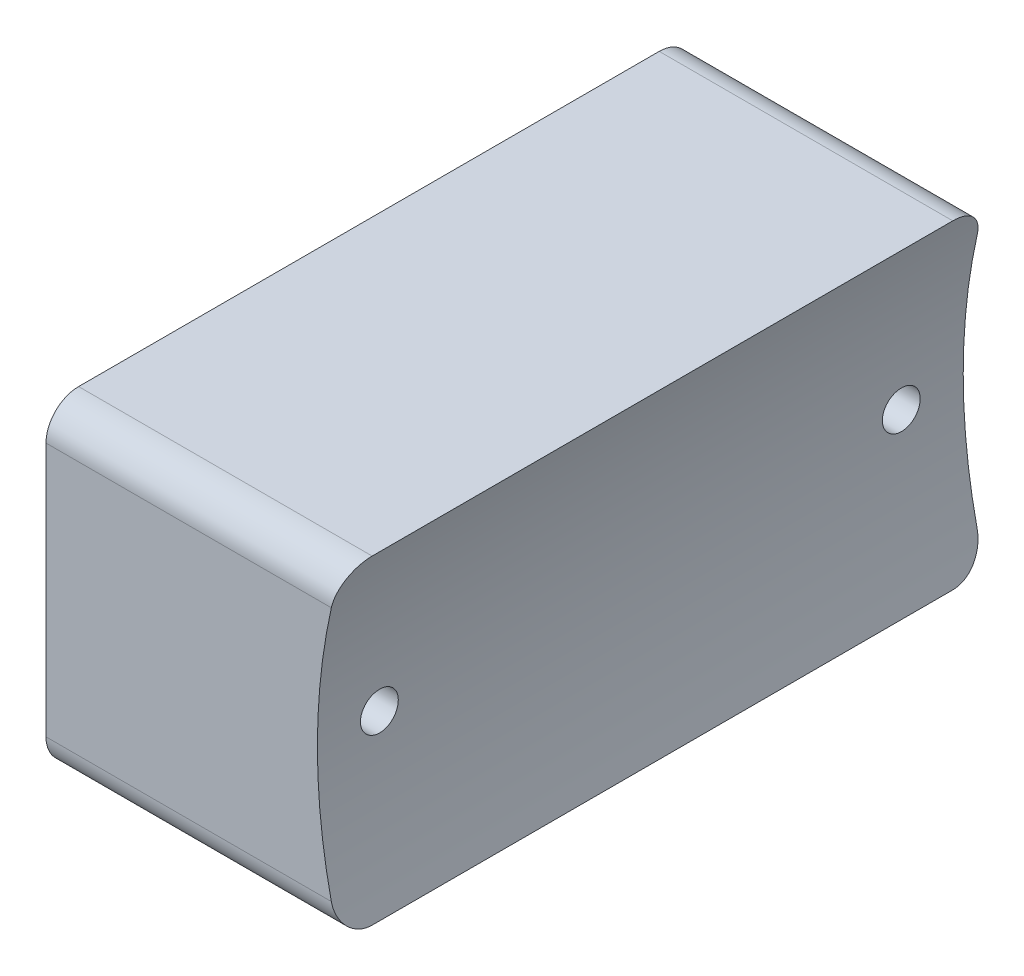
SolidWorks part; units mm, degrees
ref_plane "Спереди" through (0, 0, 0) normal (0, 0, 1) x (1, 0, 0)
ref_plane "Сверху" through (0, 0, 0) normal (0, 1, 0) x (1, 0, 0)
ref_plane "Справа" through (0, 0, 0) normal (1, 0, 0) x (0, 0, -1)
sketch "Эскиз1" plane through (0, 0, 0) normal (1, 0, 0) x (0, 0, -1)
  line L0 (-1050, 0) -> (48950, 0) construction
  line L1 (0, -1021.7777) -> (0, 48978.2223) construction
  line L2 (-24.75, -12.25) -> (24.75, -12.25)
  line L3 (-24.75, -12.25) -> (-24.75, 12.25)
  line L4 (-24.75, 12.25) -> (24.75, 12.25)
  line L5 (24.75, -12.25) -> (24.75, 12.25)
  line L6 (-24.75, -12.25) -> (24.75, 12.25) construction
  line L7 (-24.75, 12.25) -> (24.75, -12.25) construction
  point P3 (0, 0)
  dimension "D1" = 24.5
  dimension "D2" = 49.5
extrude "Бобышка-Вытянуть1" add sketch "Эскиз1" along normal blind 22.5
sketch "Эскиз2" plane through (0, 0, 0) normal (-1, 0, 0) x (0, 0, 1)
  line L1 (-24.75, -12.25) -> (-24.75, 12.25) construction
  line L2 (24.75, 12.25) -> (24.75, -12.25) construction
  line L3 (24.75, -12.25) -> (-24.75, -12.25) construction
  circle A0 centre (-20, -7.25) radius 2.5
  circle A1 centre (20, -7.25) radius 2.5
  dimension "D3" = 5
  dimension "D1" = 5
  dimension "D2" = 4.75
  dimension "D4" = 4.75
  dimension "D5" = 5
extrude "Вырез-Вытянуть1" cut sketch "Эскиз2" against normal blind 3
sketch "Эскиз3" plane through (0, 0, 0) normal (-1, 0, 0) x (0, 0, 1)
  line L0 (0, -1000) -> (0, 49000) construction
  line L2 (-7.6, 7.5) -> (7.6, 7.5)
  line L3 (-7.6, 7.5) -> (-7.6, 10)
  line L4 (-7.6, 10) -> (7.6, 10)
  line L5 (7.6, 7.5) -> (7.6, 10)
  line L6 (-7.6, 7.5) -> (7.6, 10) construction
  line L7 (-7.6, 10) -> (7.6, 7.5) construction
  line L8 (-24.75, 12.25) -> (24.75, 12.25) construction
  point P1 (0, 8.75)
  dimension "D1" = 15.2
  dimension "D2" = 2.5
  dimension "D3" = 2.25
extrude "Вырез-Вытянуть2" cut sketch "Эскиз3" against normal blind 8
sketch "Эскиз4" plane through (0, 0, -24.75) normal (0, 0, -1) x (-1, 0, 0)
  line L2 (-22.5, 12.25) -> (-22.5, -12.25)
  arc A0 (-38.4051, 35.7) -> (-38.4051, -35.7) centre (-65.8005, 0) cw construction
  arc A1 (-22.5, 12.25) -> (-22.5, -12.25) centre (-65.8005, 0) cw
  dimension "D1" = 71.4
  dimension "D2" = 45
extrude "Вырез-Вытянуть3" cut sketch "Эскиз4" against normal blind 50
sketch "Эскиз5" plane through (0, 0, 0) normal (1, 0, 0) x (0, 0, -1)
  line L0 (-1000, 0) -> (49000, 0) construction
  circle A0 centre (-20, 0) radius 1.45
  circle A1 centre (20, 0) radius 1.45
  dimension "D1" = 2.9
  dimension "D2" = 20
  dimension "D3" = 20
extrude "Вырез-Вытянуть4" cut sketch "Эскиз5" against normal blind 10 from offset 22.5
fillet "Скругление1" radius 2.5 4 edges at (11.25, -12.25, 24.75) (11.25, 12.25, 24.75) (11.25, -12.25, -24.75) (11.25, 12.25, -24.75)
